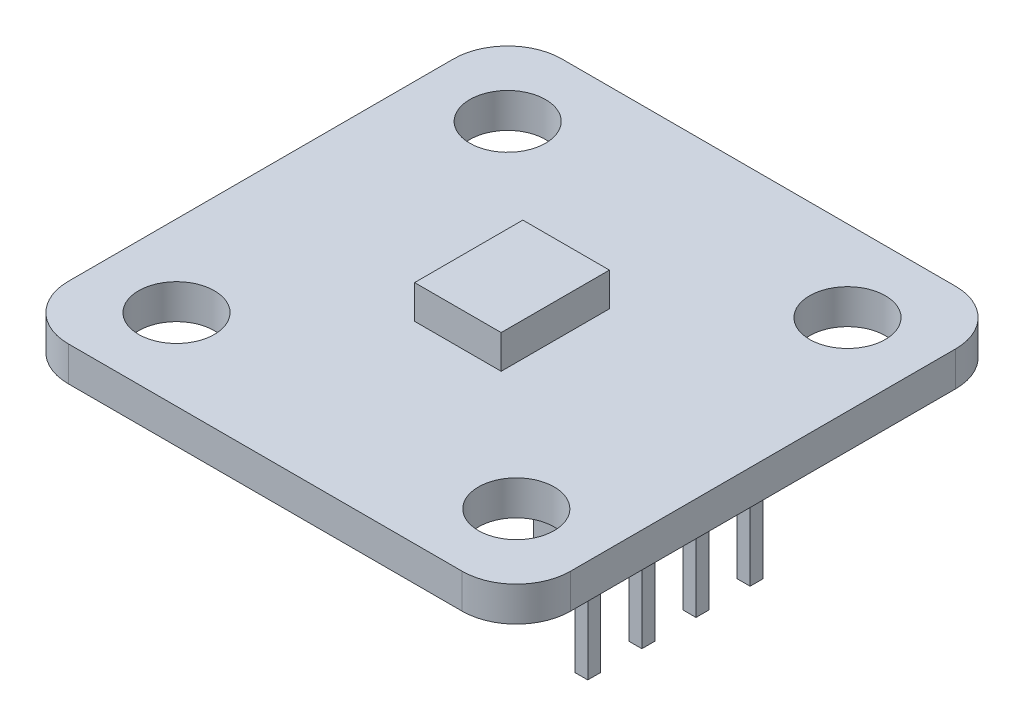
SolidWorks part; units mm, degrees
ref_plane "Front Plane" through (0, 0, 0) normal (0, 0, 1) x (1, 0, 0)
ref_plane "Top Plane" through (0, 0, 0) normal (0, 1, 0) x (1, 0, 0)
ref_plane "Right Plane" through (0, 0, 0) normal (1, 0, 0) x (0, 0, -1)
sketch "Sketch1" plane through (0, 0, 0) normal (0, 1, 0) x (1, 0, 0)
  line L1 (-11.6, -11.4) -> (11.6, -11.4)
  line L2 (-11.6, -11.4) -> (-11.6, 11.4)
  line L3 (-11.6, 11.4) -> (11.6, 11.4)
  line L4 (11.6, -11.4) -> (11.6, 11.4)
  line L5 (-11.6, -11.4) -> (11.6, 11.4) construction
  line L6 (-11.6, 11.4) -> (11.6, -11.4) construction
  line L7 (-2, -2.5) -> (2, -2.5)
  line L8 (-2, -2.5) -> (-2, 2.5)
  line L9 (-2, 2.5) -> (2, 2.5)
  line L10 (2, -2.5) -> (2, 2.5)
  line L11 (-2, -2.5) -> (2, 2.5) construction
  line L12 (-2, 2.5) -> (2, -2.5) construction
  point P0 (0, 0)
  point P5 (0, 0)
  dimension "D1" = 23.2
  dimension "D2" = 22.8
  dimension "D3" = 5
  dimension "D4" = 4
extrude "Boss-Extrude1" add sketch "Sketch1" along normal blind 1.6 contours L1 L4 L3 L2 L10 L7 L8 L9 region at (-11.2747, 0, 0)
extrude "Boss-Extrude2" add sketch "Sketch1<4>" along normal blind 3.15 contours L7 L10 L9 L8 region at (0, 0, 0)
sketch "Sketch1<4>" plane through (0, 0, 0) normal (0, 1, 0) x (1, 0, 0) same geometry as "Sketch1"
fillet "Fillet1" radius 2.5 4 edges at (-11.6, 0.8, -11.4) (-11.6, 0.8, 11.4) (11.6, 0.8, -11.4) (11.6, 0.8, 11.4)
sketch "Sketch2" plane through (0, 1.6, 0) normal (0, 1, 0) x (1, 0, 0)
  line L0 (0, -11.4) -> (0, 11.4) construction
  line L1 (-9.1, -11.4) -> (9.1, -11.4) construction
  line L2 (-9.1, 11.4) -> (9.1, 11.4) construction
  line L3 (-11.6, -8.9) -> (-11.6, 8.9) construction
  line L4 (-11.6, 0) -> (11.6, 0) construction
  line L5 (11.6, -8.9) -> (11.6, 8.9) construction
  circle A1 centre (-7.85, -7.65) radius 1.75
  circle A2 centre (-7.85, 7.65) radius 1.75
  circle A3 centre (7.85, -7.65) radius 1.75
  circle A4 centre (7.85, 7.65) radius 1.75
  point P2 (-7.85, -9.4)
  point P3 (-7.85, -5.9)
  point P4 (-6.1, -7.65)
  point P5 (-9.6, -7.65)
  dimension "D1" = 2
  dimension "D3" = 2
  dimension "D2" = 3.5
extrude "Cut-Extrude1" cut sketch "Sketch2" against normal blind 3.1
sketch "Sketch3" plane through (0, 0, 0) normal (0, -1, 0) x (1, 0, 0)
  line L0 (-9.1, -11.4) -> (9.1, -11.4) construction
  line L1 (11.6, 8.9) -> (11.6, -8.9) construction
  line L2 (-11.6, 8.9) -> (-11.6, -8.9) construction
  line L3 (5.6, 4.6) -> (8.1, 4.6)
  line L4 (5.6, 4.6) -> (5.6, -5.4)
  line L5 (5.6, -5.4) -> (8.1, -5.4)
  line L6 (8.1, 4.6) -> (8.1, -5.4)
  line L7 (-8.1, 3.6) -> (-5.6, 3.6)
  line L8 (-8.1, 3.6) -> (-8.1, -3.9)
  line L9 (-8.1, -3.9) -> (-5.6, -3.9)
  line L10 (-5.6, 3.6) -> (-5.6, -3.9)
  point P0 (5.6, 4.6)
  dimension "D1" = 16
  dimension "D2" = 6
  dimension "D3" = 10
  dimension "D4" = 2.5
  dimension "D5" = 15
  dimension "D6" = 2.5
  dimension "D7" = 6
  dimension "D8" = 7.5
extrude "Boss-Extrude3" add sketch "Sketch3" along normal blind 2.6
sketch "Sketch4" plane through (0, -2.6, 0) normal (0, -1, 0) x (1, 0, 0)
  line L0 (-8.1, 2.35) -> (-5.6, 2.35) construction
  line L1 (-6.55, -0.45) -> (-7.15, -0.45)
  line L2 (-6.55, -0.45) -> (-6.55, 0.15)
  line L3 (-6.55, 0.15) -> (-7.15, 0.15)
  line L4 (-7.15, -0.45) -> (-7.15, 0.15)
  line L5 (-5.6, 3.6) -> (-8.1, 3.6) construction
  line L6 (-8.1, 3.6) -> (-8.1, -3.9) construction
  line L7 (-6.55, -0.45) -> (-7.15, 0.15) construction
  line L8 (-6.85, 3.6) -> (-6.85, -3.9) construction
  line L9 (-6.55, 2.05) -> (-7.15, 2.05)
  line L10 (-6.55, 2.05) -> (-6.55, 2.65)
  line L11 (-6.55, 2.65) -> (-7.15, 2.65)
  line L12 (-7.15, 2.05) -> (-7.15, 2.65)
  line L13 (-6.55, 2.05) -> (-7.15, 2.65) construction
  line L14 (-6.55, 2.65) -> (-7.15, 2.05) construction
  line L15 (-8.1, -3.9) -> (-5.6, -3.9) construction
  line L16 (-5.6, -3.9) -> (-5.6, 3.6) construction
  line L17 (-8.1, -0.15) -> (-5.6, -0.15) construction
  line L18 (-8.1, 3.6) -> (-8.1, -3.9) construction
  line L19 (-8.1, -2.65) -> (-5.6, -2.65) construction
  line L20 (-6.55, 0.15) -> (-7.15, -0.45) construction
  line L21 (-5.6, -3.9) -> (-5.6, 3.6) construction
  line L22 (-6.55, -2.95) -> (-7.15, -2.95)
  line L23 (-6.55, -2.95) -> (-6.55, -2.35)
  line L24 (-8.1, -3.9) -> (-5.6, -3.9) construction
  line L25 (-6.55, -2.35) -> (-7.15, -2.35)
  line L26 (-7.15, -2.95) -> (-7.15, -2.35)
  line L27 (-6.55, -2.95) -> (-7.15, -2.35) construction
  line L28 (-6.55, -2.35) -> (-7.15, -2.95) construction
  line L29 (6.85, 4.6) -> (6.85, -5.4) construction
  line L30 (8.1, 4.6) -> (5.6, 4.6) construction
  line L31 (5.6, -5.4) -> (8.1, -5.4) construction
  line L33 (8.1, 4.6) -> (5.6, 4.6) construction
  line L34 (7.15, 3.05) -> (6.55, 3.05)
  line L35 (7.15, 3.05) -> (7.15, 3.65)
  line L36 (7.15, 3.65) -> (6.55, 3.65)
  line L37 (6.55, 3.05) -> (6.55, 3.65)
  line L38 (7.15, 3.05) -> (6.55, 3.65) construction
  line L39 (7.15, 3.65) -> (6.55, 3.05) construction
  line L40 (7.15, 0.55) -> (6.55, 0.55)
  line L41 (7.15, 0.55) -> (7.15, 1.15)
  line L42 (7.15, 1.15) -> (6.55, 1.15)
  line L43 (6.55, 0.55) -> (6.55, 1.15)
  line L44 (7.15, 0.55) -> (6.55, 1.15) construction
  line L45 (7.15, 1.15) -> (6.55, 0.55) construction
  line L46 (7.15, -1.95) -> (6.55, -1.95)
  line L47 (7.15, -1.95) -> (7.15, -1.35)
  line L48 (7.15, -1.35) -> (6.55, -1.35)
  line L49 (6.55, -1.95) -> (6.55, -1.35)
  line L50 (7.15, -1.95) -> (6.55, -1.35) construction
  line L51 (7.15, -1.35) -> (6.55, -1.95) construction
  line L52 (7.15, -4.45) -> (6.55, -4.45)
  line L53 (7.15, -4.45) -> (7.15, -3.85)
  line L54 (7.15, -3.85) -> (6.55, -3.85)
  line L55 (6.55, -4.45) -> (6.55, -3.85)
  line L56 (7.15, -4.45) -> (6.55, -3.85) construction
  line L57 (7.15, -3.85) -> (6.55, -4.45) construction
  point P12 (-6.85, 2.35)
  point P24 (-6.85, -0.15)
  point P33 (-6.85, -2.65)
  point P45 (6.85, 3.35)
  point P52 (6.85, 0.85)
  point P57 (6.85, -1.65)
  point P62 (6.85, -4.15)
  dimension "D1" = 1.25
  dimension "D2" = 3.75
  dimension "D3" = 0.6
  dimension "D4" = 0.6
  dimension "D5" = 1.25
  dimension "D6" = 3
  dimension "D7" = 0.6
  dimension "D8" = 1.25
  dimension "D9" = 4
extrude "Boss-Extrude4" add sketch "Sketch4" along normal blind 5
